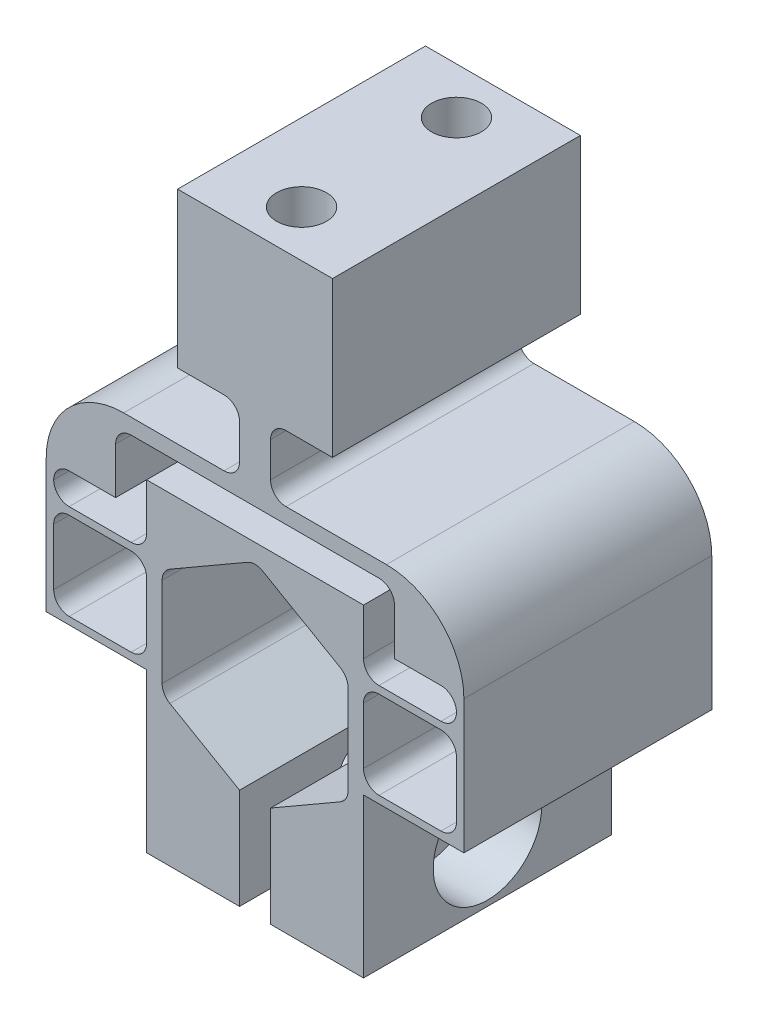
SolidWorks part; units mm, degrees
ref_plane "Front Plane" through (0, 0, 0) normal (0, 0, 1) x (1, 0, 0)
ref_plane "Top Plane" through (0, 0, 0) normal (0, 1, 0) x (1, 0, 0)
ref_plane "Right Plane" through (0, 0, 0) normal (1, 0, 0) x (0, 0, -1)
sketch "Sketch1" plane through (0, 0, 0) normal (0, 0, 1) x (1, 0, 0)
  line L0 (-11.1125, 12.7) -> (11.1125, -12.7) construction
  line L1 (-11.1125, 12.7) -> (11.1125, 12.7)
  line L2 (-11.1125, 12.7) -> (-11.1125, -12.7)
  line L3 (-11.1125, -12.7) -> (11.1125, -12.7)
  line L4 (11.1125, 12.7) -> (11.1125, -12.7)
  line L6 (0, 10.9985) -> (-9.525, 5.4993)
  line L7 (-9.525, 5.4993) -> (-9.525, -5.4993)
  line L8 (-9.525, -5.4993) -> (0, -10.9985)
  line L9 (0, -10.9985) -> (9.525, -5.4993)
  line L10 (9.525, -5.4993) -> (9.525, 5.4993)
  line L11 (9.525, 5.4993) -> (0, 10.9985)
  circle A1 centre (0, 0) radius 9.525 construction
  dimension "D2" = 22.225
  dimension "D3" = 25.4
  dimension "D4" = 19.05
extrude "Extrude1" add sketch "Sketch1" along normal mid plane 25.4
sketch "Sketch2" plane through (0, 0, 12.7) normal (0, 0, 1) x (1, 0, 0)
  line L1 (11.1125, 6.35) -> (20.6375, 6.35)
  line L2 (11.1125, 6.35) -> (11.1125, 5.588)
  line L3 (11.1125, 5.588) -> (20.6375, 5.588)
  line L4 (20.6375, 6.35) -> (20.6375, 5.588)
  line L5 (20.6375, -4.1538) -> (20.6375, -3.3918)
  line L6 (11.1125, -3.3918) -> (20.6375, -3.3918)
  line L7 (11.1125, -4.1538) -> (11.1125, -3.3918)
  line L8 (11.1125, -4.1538) -> (20.6375, -4.1538)
  line L9 (0, 56.3914) -> (0, -56.3914) construction
  line L10 (-11.1125, -4.1538) -> (-20.6375, -4.1538)
  line L11 (-11.1125, -4.1538) -> (-11.1125, -3.3918)
  line L12 (-11.1125, -3.3918) -> (-20.6375, -3.3918)
  line L13 (-20.6375, -4.1538) -> (-20.6375, -3.3918)
  line L14 (-20.6375, 6.35) -> (-20.6375, 5.588)
  line L15 (-11.1125, 5.588) -> (-20.6375, 5.588)
  line L16 (-11.1125, 6.35) -> (-11.1125, 5.588)
  line L17 (-11.1125, 6.35) -> (-20.6375, 6.35)
  line L20 (11.1125, 12.7) -> (-11.1125, 12.7) construction
  line L21 (11.1125, -12.7) -> (11.1125, 12.7) construction
  dimension "D1" = 0.762
  dimension "D2" = 9.525
  dimension "D3" = 6.35
extrude "Extrude2" add sketch "Sketch2" against normal up to surface (25.4 mm away) up to face at (0, 0, -12.7)
sketch "Sketch3" plane through (0, 0, 12.7) normal (0, 0, 1) x (1, 0, 0)
  line L0 (0, 20.2554) -> (0, -20.2554) construction
  line L1 (20.6375, -4.1538) -> (21.3995, -4.1538)
  line L2 (20.6375, -4.1538) -> (20.6375, 9.525)
  line L3 (20.6375, 9.525) -> (21.3995, 9.525)
  line L4 (21.3995, -4.1538) -> (21.3995, 9.525)
  line L5 (-21.3995, -4.1538) -> (-21.3995, 9.525)
  line L6 (-20.6375, 9.525) -> (-21.3995, 9.525)
  line L7 (-20.6375, -4.1538) -> (-20.6375, 9.525)
  line L8 (-20.6375, -4.1538) -> (-21.3995, -4.1538)
  line L10 (11.1125, 12.7) -> (-11.1125, 12.7) construction
  dimension "D1" = 0.762
  dimension "D2" = 3.175
extrude "Extrude3" add sketch "Sketch3" against normal up to surface (25.4 mm away) up to face at (0, 0.8785, -12.7)
sketch "Sketch4" plane through (0, 0, 12.7) normal (0, 0, 1) x (1, 0, 0)
  line L0 (0, -22.1299) -> (0, 22.1299) construction
  line L1 (-21.3995, 17.4625) -> (21.3995, 17.4625)
  line L2 (-21.3995, 17.4625) -> (-21.3995, 9.525)
  line L3 (-21.3995, 9.525) -> (-14.2875, 9.525)
  line L4 (21.3995, 17.4625) -> (21.3995, 9.525)
  line L5 (-20.6375, 9.525) -> (-21.3995, 9.525) construction
  line L6 (-21.3995, 9.525) -> (-21.3995, -4.1538) construction
  line L7 (-14.2875, 9.525) -> (-14.2875, 15.875)
  line L8 (-14.2875, 15.875) -> (14.2875, 15.875)
  line L9 (14.2875, 9.525) -> (14.2875, 15.875)
  line L10 (14.2875, 9.525) -> (21.3995, 9.525)
  line L12 (11.1125, 12.7) -> (-11.1125, 12.7) construction
  line L13 (-11.1125, 12.7) -> (-11.1125, 6.35) construction
  point P15 (0, 15.875)
  dimension "D1" = 3.175
  dimension "D2" = 7.9375
  dimension "D3" = 3.175
extrude "Extrude4" add sketch "Sketch4" against normal up to surface (25.4 mm away) up to face at (-17.0656, 2.2206, -12.7)
sketch "Sketch7" plane through (0, 17.4625, 0) normal (0, 1, 0) x (1, 0, 0)
  line L0 (-21.3995, 12.7) -> (21.3995, 12.7) construction
  line L1 (-1.5875, 12.7) -> (1.5875, 12.7)
  line L2 (-1.5875, 12.7) -> (-1.5875, -12.7)
  line L3 (-1.5875, -12.7) -> (1.5875, -12.7)
  line L4 (1.5875, 12.7) -> (1.5875, -12.7)
  line L5 (21.3995, -12.7) -> (-21.3995, -12.7) construction
  line L6 (0, 0) -> (0, -12.7) construction
  dimension "D1" = 3.175
extrude "Extrude5" add sketch "Sketch7" along normal blind 6.7462
sketch "Sketch8" plane through (0, 0, 12.7) normal (0, 0, 1) x (1, 0, 0)
  line L0 (-1.5875, 24.2087) -> (1.5875, 24.2087) construction
  line L1 (-7.9375, 40.0837) -> (7.9375, 40.0837)
  line L2 (-7.9375, 40.0837) -> (-7.9375, 24.2087)
  line L3 (-7.9375, 24.2087) -> (7.9375, 24.2087)
  line L4 (7.9375, 40.0837) -> (7.9375, 24.2087)
  line L5 (0, 0) -> (0, 49.5777) construction
  dimension "D1" = 15.875
  dimension "D2" = 40.0837
  dimension "D3" = 15.875
extrude "Extrude6" add sketch "Sketch8" against normal up to surface (25.4 mm away) up to face at (-1.2224, 6.9165, -12.7)
hole_wizard "1/4-20 Tapped Hole1" positions "Sketch6" profile "Sketch5" tap size "1/4-20" standard "Ansi Inch"
sketch "Sketch6" plane through (-10.9786, 40.0837, -1.6694) normal (0, 1, 0) x (-1, 0, 0)
  line L2 (-10.9786, -11.0306) -> (-10.9786, 14.3694) construction
  line L9 (-3.0411, -11.0306) -> (-18.9161, -11.0306) construction
  line L10 (-10.9786, 1.6694) -> (-18.9161, 1.6694) construction
  line L11 (-18.9161, -11.0306) -> (-18.9161, 14.3694) construction
  point P0 (-10.9786, -6.2681)
  point P1 (-10.9786, 9.6069)
  dimension "D1" = 15.875
cosmetic thread "Hole Thread1" parameters "D1"=9.525, "D2"=6.35
cosmetic thread "Hole Thread2" parameters "D1"=9.525, "D2"=6.35
sketch "Sketch5" plane through (0, 40.0837, -7.9375) normal (1, 0, 0) x (0, 0, 1)
  line L0 (0, 0) -> (0, 11.0588)
  line L1 (0, 11.0588) -> (2.5527, 9.525)
  line L2 (2.5527, 9.525) -> (2.5527, 0)
  line L5 (2.5527, 0) -> (0, 0)
  line L10 (0, 11.0588) -> (-2.5527, 9.525) construction
  line L11 (0, -6.35) -> (0, 107.95) construction
  dimension "Tap Drill Dia." = 5.1054
  dimension "Tap Drill Depth" = 9.525
  dimension "Drill Angle" = 118
sketch "Sketch9" plane through (0, 0, 12.7) normal (0, 0, 1) x (1, 0, 0)
  line L0 (-1.5875, -10.082) -> (-1.5875, -12.7)
  line L2 (-1.5875, -12.7) -> (1.5875, -12.7)
  line L3 (1.5875, -12.7) -> (1.5875, -10.082)
  line L4 (-11.1125, -12.7) -> (11.1125, -12.7) construction
  line L5 (-9.525, -5.4993) -> (0, -10.9985) construction
  line L6 (-1.5875, -10.082) -> (0, -10.9985)
  line L7 (0, -10.9985) -> (1.5875, -10.082)
  line L8 (0, -10.9985) -> (9.525, -5.4993) construction
  dimension "D1" = 3.175
extrude "Extrude7" cut sketch "Sketch9" against normal through all
sketch "Sketch10" plane through (0, 0, 12.7) normal (0, 0, 1) x (1, 0, 0)
  line L0 (0, 0) -> (0, -33.1376) construction
  line L1 (1.5875, -12.7) -> (11.1125, -12.7)
  line L2 (1.5875, -12.7) -> (11.1125, -12.7) construction
  line L3 (11.1125, -12.7) -> (11.1125, -20.4007)
  line L4 (11.1125, -20.4007) -> (1.5875, -20.4007)
  line L5 (1.5875, -12.7) -> (1.5875, -20.4007)
  line L6 (-1.5875, -12.7) -> (-1.5875, -20.4007)
  line L7 (-11.1125, -20.4007) -> (-1.5875, -20.4007)
  line L8 (-11.1125, -12.7) -> (-11.1125, -20.4007)
  line L9 (-1.5875, -12.7) -> (-11.1125, -12.7)
  line L10 (11.1125, -3.3918) -> (11.1125, 5.588) construction
  dimension "D1" = 10.3187
extrude "Extrude8" add sketch "Sketch10" against normal up to surface (25.4 mm away) up to face at (-17.0656, 2.2206, -12.7)
hole_wizard "CBORE for 1/4 Socket Head Cap Screw1" positions "Sketch12" profile "Sketch11" counterbore size "1/4" standard "Ansi Inch" end condition up to next
sketch "Sketch12" plane through (11.1125, 0, 0) normal (1, 0, 0) x (0, 0, -1)
  line L9 (0, -20.4007) -> (0, -4.1538) construction
  line L10 (12.7, -20.4007) -> (-12.7, -20.4007) construction
  line L11 (12.7, -4.1538) -> (-12.7, -4.1538) construction
  circle A0 centre (0, -14.2875) radius 6.35 construction
  point P0 (0, -14.2875)
  dimension "D1" = 12.7
  dimension "D2" = 14.2875
sketch "Sketch11" plane through (11.1125, -14.2875, 0) normal (0, 1, 0) x (0, 0, -1)
  line L0 (0, 0) -> (0, 9.525)
  line L1 (0, 9.525) -> (3.3782, 9.525)
  line L3 (3.3782, 9.525) -> (3.3782, 6.35)
  line L4 (3.3782, 6.35) -> (5.5562, 6.35)
  line L5 (5.5562, 6.35) -> (5.5562, 0)
  line L7 (5.5562, 0) -> (0, 0)
  line L11 (0, -6.35) -> (0, 107.95) construction
  dimension "Thru Hole Dia." = 6.7564
  dimension "Thru Hole Depth" = 9.525
  dimension "C'Bore Dia." = 11.1125
  dimension "C'Bore Depth" = 6.35
hole_wizard "1/4-20 Tapped Hole2" positions "Sketch14" profile "Sketch13" tap size "1/4-20" standard "Ansi Inch" end condition up to next
sketch "Sketch14" plane through (-11.1125, 0, 0) normal (-1, 0, 0) x (0, 0, 1)
  point P0 (0, -14.2875)
sketch "Sketch13" plane through (-11.1125, -14.2875, 0) normal (0, 1, 0) x (0, 0, 1)
  line L0 (0, 0) -> (0, 9.525)
  line L1 (0, 9.525) -> (2.5527, 9.525)
  line L2 (2.5527, 9.525) -> (2.5527, 0)
  line L5 (2.5527, 0) -> (0, 0)
  line L11 (0, -6.35) -> (0, 107.95) construction
  dimension "Thru Tap Drill Dia." = 5.1054
  dimension "Thru Tap Drill Depth" = 9.525
cosmetic thread "Hole Thread3" parameters "D2"=6.35
fillet "Fillet1" radius 1.5875 25 edges at (20.6375, -3.3918, 0) (-11.1125, 5.588, 0) (20.6375, 5.588, 0) (11.1125, -3.3918, 0) (-20.6375, -3.3918, 0) (-20.6375, 6.35, 0) (-20.6375, 9.525, 0) (-20.6375, 5.588, 0) (9.525, -5.4993, 0) (9.525, 5.4993, 0) (0, 10.9985, 0) (-9.525, 5.4993, 0) (-9.525, -5.4993, 0) (-11.1125, 6.35, 0) (-14.2875, 15.875, 0) (14.2875, 15.875, 0) (20.6375, 6.35, 0) (20.6375, 9.525, 0)
sketch "Sketch15" plane through (0, 0, 12.7) normal (0, 0, 1) x (1, 0, 0)
  circle A0 centre (0, 0) radius 10.7529 construction
  arc A1 (0.7937, 10.5403) -> (-0.7938, 10.5403) centre (0, 9.1654) ccw construction
  dimension "D1" = 21.5059
fillet "Fillet2" radius 7.9375 2 edges at (21.3995, 17.4625, 0) (-21.3995, 17.4625, 0)
